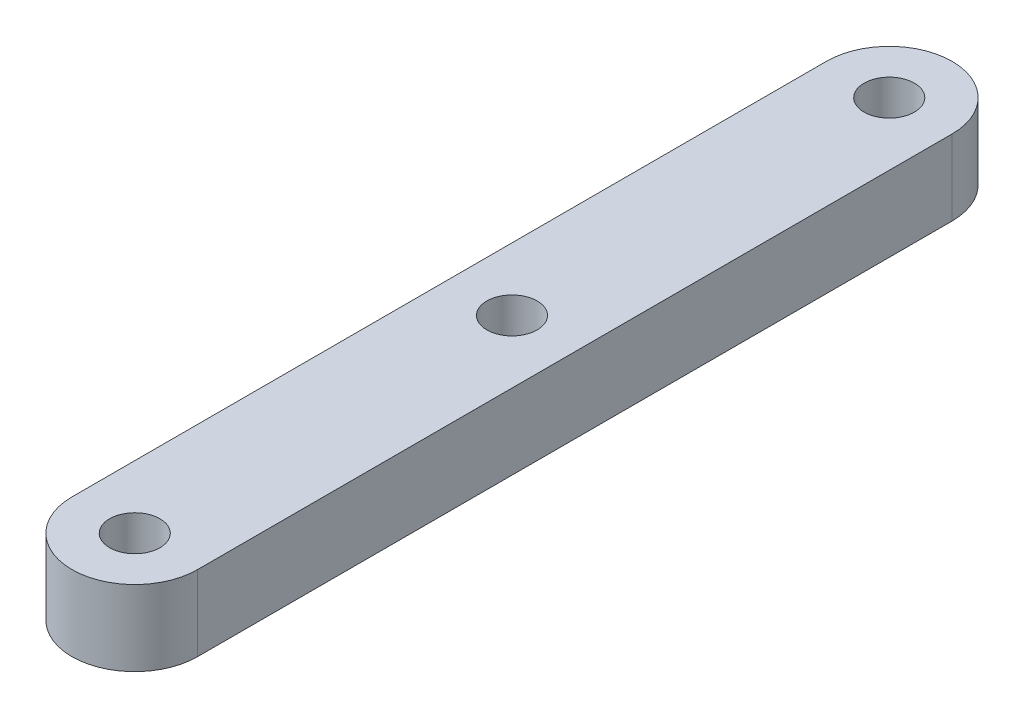
SolidWorks part; units mm, degrees
ref_plane "Front Plane" through (0, 0, 0) normal (0, 0, 1) x (1, 0, 0)
ref_plane "Top Plane" through (0, 0, 0) normal (0, 1, 0) x (1, 0, 0)
ref_plane "Right Plane" through (0, 0, 0) normal (1, 0, 0) x (0, 0, -1)
sketch "Sketch1" plane through (0, 0, 0) normal (0, 1, 0) x (1, 0, 0)
  line L0 (0, 15) -> (0, -15) construction
  line L1 (2.5, 15) -> (2.5, -15)
  line L2 (-2.5, 15) -> (-2.5, -15)
  arc A0 (2.5, 15) -> (-2.5, 15) centre (0, 15) ccw
  arc A1 (-2.5, -15) -> (2.5, -15) centre (0, -15) ccw
  circle A2 centre (0, 15) radius 1
  circle A3 centre (0, -15) radius 1
  circle A4 centre (0, 0) radius 1
  point P2 (0, 0)
  dimension "D3" = 2
  dimension "D1" = 30
  dimension "D2" = 5
extrude "Boss-Extrude1" add sketch "Sketch1" along normal blind 3
